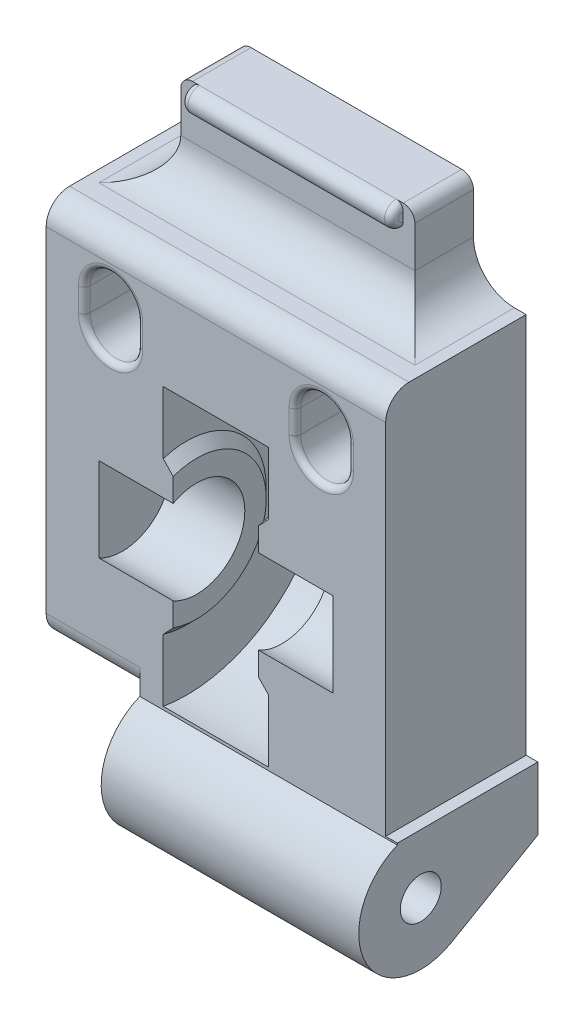
SolidWorks part; units mm, degrees
ref_plane "Front Plane" through (0, 0, 0) normal (0, 0, 1) x (1, 0, 0)
ref_plane "Top Plane" through (0, 0, 0) normal (0, 1, 0) x (1, 0, 0)
ref_plane "Right Plane" through (0, 0, 0) normal (1, 0, 0) x (0, 0, -1)
sketch "Sketch1" plane through (0, 0, 0) normal (1, 0, 0) x (0, 0, -1)
  line L0 (10, -0.346) -> (2.5517, -4.6453)
  line L1 (-2, 37.654) -> (10, 37.654)
  line L2 (-2, 37.654) -> (-2, 4.9082)
  line L3 (10, -0.346) -> (-2, -0.346) construction
  line L4 (10, 37.654) -> (10, -0.346)
  line L5 (-2, -0.346) -> (-2, 4.9082) construction
  arc A0 (-2, 4.9082) -> (2.5517, -4.6453) centre (0, 0) ccw
  dimension "D1" = 5.3
  dimension "D2" = 12
  dimension "D3" = 2
  dimension "D4" = 38
  dimension "D5" = 0.346
extrude "Boss-Extrude1" add sketch "Sketch1" along normal mid plane 32
sketch "Sketch2" plane through (0, 0, 0) normal (1, 0, 0) x (0, 0, -1)
  circle A0 centre (0, 17) radius 12
  dimension "D3" = 24
  dimension "D1" = 17
extrude "Cut-Extrude1" cut sketch "Sketch2" against normal mid plane 9
sketch "Sketch6" plane through (0, 0, 0) normal (1, 0, 0) x (0, 0, -1)
  circle A0 centre (0, 0) radius 1.75
  dimension "D1" = 3.5
sketch "Sketch8" plane through (-4.5, 0, 0) normal (1, 0, 0) x (0, 0, -1)
  line L0 (-2, 23.4992) -> (-2, 10.5008)
  line L3 (-2, 37.654) -> (-2, 4.9082) construction
  arc A0 (-2, 10.5008) -> (-2, 23.4992) centre (0, 17) ccw
  arc A1 (10, 23.6332) -> (-2, 28.8322) centre (0, 17) ccw construction
  dimension "D1" = 6.8
sketch "Sketch9" plane through (4.5, 0, 0) normal (-1, 0, 0) x (0, 0, 1)
  line L0 (2, 23.4992) -> (2, 10.5008)
  arc A0 (2, 23.4992) -> (2, 10.5008) centre (0, 17) ccw
extrude "Cut-Extrude4" cut sketch "Sketch6" against normal mid plane 35
extrude "Boss-Extrude2" add sketch "Sketch8" along normal blind 0.85
extrude "Boss-Extrude3" add sketch "Sketch9" along normal blind 0.85
sketch "Sketch3" plane through (0, 0, 0) normal (1, 0, 0) x (0, 0, -1)
  circle A0 centre (0, 17) radius 4.12
  dimension "D1" = 8.24
extrude "bearing_axis" cut sketch "Sketch3" against normal mid plane 20
chamfer "Chamfer1" distance 0.85 angle 45 2 edges at (3.65, 17, -6.8) (-3.65, 17, -6.8)
sketch "Sketch15" plane through (0, 37.654, 0) normal (0, 1, 0) x (1, 0, 0)
  line L0 (16, 10) -> (-16, 10) construction
  line L2 (-10, 10) -> (-10, 5)
  line L3 (-10, 5) -> (10, 5)
  line L4 (10, 10) -> (10, 5)
  line L5 (0, 10) -> (10, 5) construction
  line L6 (-10, 5) -> (0, 10) construction
  line L7 (-10, 10) -> (10, 10)
  point P0 (0, 10)
  dimension "D1" = 5
  dimension "D2" = 20
extrude "Boss-Extrude4" add sketch "Sketch15" along normal blind 8
fillet "Fillet1" radius 3.5 3 edges at (0, 37.654, -5)
fillet "Fillet3" radius 1 2 edges at (-10, 45.654, -7.5) (10, 45.654, -7.5)
sketch "Sketch16" plane through (0, 0, 0) normal (1, 0, 0) x (0, 0, -1)
  circle A0 centre (5, 44.654) radius 1
extrude "Boss-Extrude5" add sketch "Sketch16" along normal mid plane 18
fillet "Fillet4" radius 0.6 2 edges at (9, 44.654, -4) (-9, 44.654, -4)
sketch "Sketch18" plane through (0, 0, -10) normal (0, 0, 1) x (1, 0, 0)
  line L0 (-9, 30.654) -> (-9, 32.654) construction
  line L1 (-11.25, 30.654) -> (-11.25, 32.654)
  line L2 (-6.75, 30.654) -> (-6.75, 32.654)
  line L3 (-16, -0.346) -> (-16, 37.654) construction
  line L5 (9, 32.654) -> (9, 30.654) construction
  line L6 (16, -0.346) -> (16, 37.654) construction
  line L7 (13.5, 37.654) -> (-13.5, 37.654) construction
  line L8 (11.25, 32.654) -> (11.25, 30.654)
  line L9 (6.75, 32.654) -> (6.75, 30.654)
  arc A0 (-11.25, 30.654) -> (-6.75, 30.654) centre (-9, 30.654) ccw
  arc A1 (-6.75, 32.654) -> (-11.25, 32.654) centre (-9, 32.654) ccw
  arc A2 (11.25, 32.654) -> (6.75, 32.654) centre (9, 32.654) ccw
  arc A3 (6.75, 30.654) -> (11.25, 30.654) centre (9, 30.654) ccw
  point P2 (-9, 31.654)
  point P14 (9, 31.654)
  dimension "D1" = 2.25
  dimension "D2" = 2
  dimension "D3" = 7
  dimension "D5" = 6
  dimension "D6" = 7
extrude "Cut-Extrude8" cut sketch "Sketch18" along normal up to surface (12 mm away) up to face at (0, 17, 2)
fillet "Fillet6" radius 0.5 8 edges at (6.75, 31.654, 2) (9, 28.404, 2) (11.25, 31.654, 2) (-11.25, 31.654, 2) (-9, 28.404, 2) (-6.75, 31.654, 2) (9, 34.904, 2) (-9, 34.904, 2)
sketch "Sketch19" plane through (16, 0, 0) normal (1, 0, 0) x (0, 0, -1)
  line L0 (10, -0.346) -> (10, 37.654) construction
  line L1 (-2, 37.654) -> (10, 37.654)
  line L2 (-2, 37.654) -> (-2, 5.054)
  line L3 (-2, 5.054) -> (10, 5.054)
  line L4 (10, 37.654) -> (10, 5.054)
  dimension "D1" = 32.6
extrude "Cut-Extrude9" cut sketch "Sketch19" against normal blind 1.5
sketch "Sketch20" plane through (-16, 0, 0) normal (-1, 0, 0) x (0, 0, 1)
  line L0 (2, 5.054) -> (-10, 5.054) construction
  line L1 (-10, 37.654) -> (2, 37.654)
  line L2 (-10, 37.654) -> (-10, 5.054)
  line L3 (-10, 5.054) -> (2, 5.054)
  line L4 (2, 37.654) -> (2, 5.054)
extrude "Cut-Extrude10" cut sketch "Sketch20" against normal blind 1.5 contours L1 L4 L3 L2
sketch "Sketch21" plane through (-16, 0, 0) normal (-1, 0, 0) x (0, 0, 1)
  line L1 (-10, 5.054) -> (6.9644, 5.054)
  line L2 (-10, 5.054) -> (-10, -5.9388)
  line L3 (-10, -5.9388) -> (6.9644, -5.9388)
  line L4 (6.9644, 5.054) -> (6.9644, -5.9388)
extrude "Cut-Extrude11" cut sketch "Sketch21" against normal blind 9.5
sketch "Sketch22" plane through (16, 0, 0) normal (1, 0, 0) x (0, 0, -1)
  line L1 (10, 5.054) -> (-7.3717, 5.054)
  line L2 (10, 5.054) -> (10, -6.2241)
  line L3 (10, -6.2241) -> (-7.3717, -6.2241)
  line L4 (-7.3717, 5.054) -> (-7.3717, -6.2241)
extrude "Cut-Extrude12" cut sketch "Sketch22" against normal blind 0.5
fillet "Fillet7" radius 2 2 edges at (0, 37.654, 2) (-10.5, 5.054, 2)
